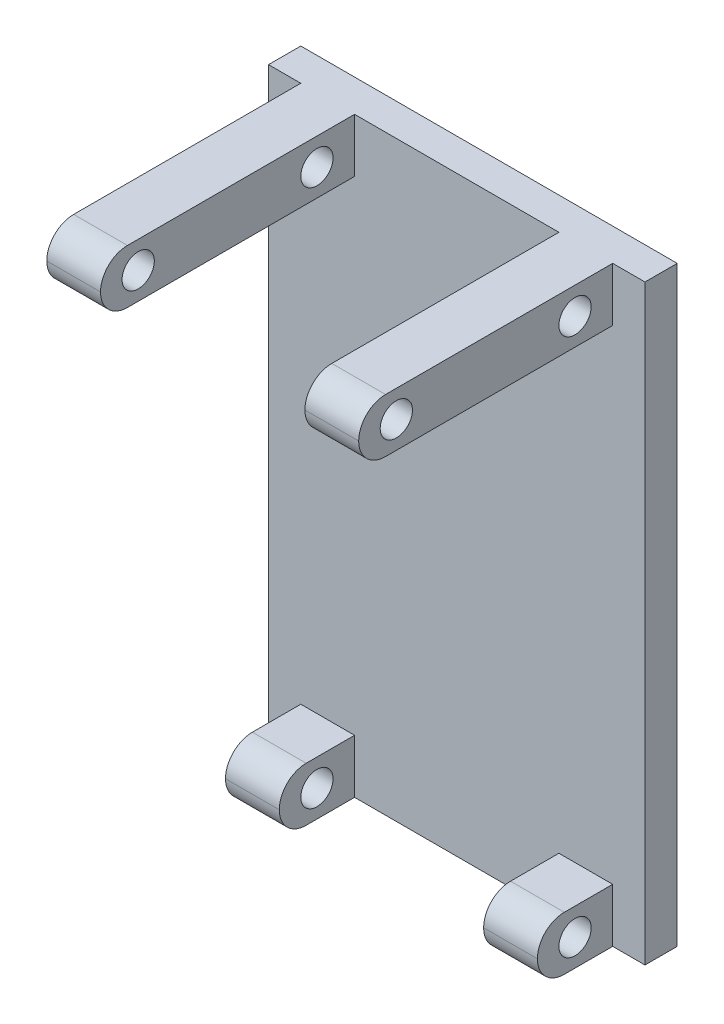
SolidWorks part; units mm, degrees
ref_plane "Front Plane" through (0, 0, 0) normal (0, 0, 1) x (1, 0, 0)
ref_plane "Top Plane" through (0, 0, 0) normal (0, 1, 0) x (1, 0, 0)
ref_plane "Right Plane" through (0, 0, 0) normal (1, 0, 0) x (0, 0, -1)
sketch "Sketch1" plane through (0, 0, 0) normal (0, 0, 1) x (1, 0, 0)
  line L1 (-17.5, -27.5) -> (17.5, -27.5)
  line L2 (-17.5, -27.5) -> (-17.5, 27.5)
  line L3 (-17.5, 27.5) -> (17.5, 27.5)
  line L4 (17.5, -27.5) -> (17.5, 27.5)
  line L5 (-17.5, -27.5) -> (17.5, 27.5) construction
  line L6 (-17.5, 27.5) -> (17.5, -27.5) construction
  point P0 (0, 0)
  dimension "D1" = 35
  dimension "D2" = 55
extrude "Boss-Extrude1" add sketch "Sketch1" along normal blind 3
sketch "Sketch2" plane through (0, 0, 3) normal (0, 0, 1) x (1, 0, 0)
  line L18 (-14.5, 27.5) -> (-9.5, 27.5)
  line L19 (-14.5, 27.5) -> (-14.5, 22.5)
  line L20 (-9.5, 27.5) -> (-9.5, 22.5)
  line L21 (-14.5, 22.5) -> (-9.5, 22.5)
  line L22 (17.5, 27.5) -> (-17.5, 27.5) construction
  line L23 (9.5, 27.5) -> (14.5, 27.5)
  line L24 (9.5, 27.5) -> (9.5, 22.5)
  line L25 (14.5, 27.5) -> (14.5, 22.5)
  line L26 (9.5, 22.5) -> (14.5, 22.5)
  line L27 (-9.5, -27.5) -> (-14.5, -27.5)
  line L28 (-9.5, -27.5) -> (-9.5, -22.5)
  line L29 (-14.5, -27.5) -> (-14.5, -22.5)
  line L30 (-9.5, -22.5) -> (-14.5, -22.5)
  line L31 (-17.5, -27.5) -> (17.5, -27.5) construction
  line L32 (9.5, -27.5) -> (14.5, -27.5)
  line L33 (9.5, -27.5) -> (9.5, -22.5)
  line L34 (14.5, -27.5) -> (14.5, -22.5)
  line L35 (9.5, -22.5) -> (14.5, -22.5)
  line L36 (-17.5, 27.5) -> (-17.5, -27.5) construction
  line L37 (17.5, -27.5) -> (17.5, 27.5) construction
  dimension "D1" = 5
  dimension "D2" = 3
  dimension "D3" = 3
  dimension "D4" = 3
  dimension "D5" = 3
  dimension "D6" = 5
extrude "Boss-Extrude2" add sketch "Sketch2" along normal blind 7
sketch "Sketch3" plane through (-14.5, 0, 0) normal (-1, 0, 0) x (0, 0, 1)
  line L0 (3, 27.5) -> (10, 22.5)
  line L1 (3, -22.5) -> (10, -27.5)
  circle A0 centre (6.5, 25) radius 1.5
  circle A1 centre (6.5, -25) radius 1.5
  dimension "D1" = 3
  dimension "D2" = 3
extrude "Cut-Extrude1" cut sketch "Sketch3" against normal up to surface (29 mm away) contours L0 A0 | L0 A0 | L1 A1 | L1 A1 region at (-14.5, 25.518, 6.87) region at (-14.5, 24.482, 6.13) region at (-14.5, -24.482, 6.87) region at (-14.5, -25.518, 6.13) up to face at (14.5, 25, 6.5)
fillet "Fillet1" radius 2.5 4 edges at (12, -27.5, 10) (12, -22.5, 10) (-12, -27.5, 10) (-12, -22.5, 10)
sketch "Sketch4" plane through (0, 0, 10) normal (0, 0, 1) x (1, 0, 0)
  line L1 (-9.5, 27.5) -> (-14.5, 27.5)
  line L2 (-9.5, 27.5) -> (-9.5, 22.5)
  line L3 (-9.5, 22.5) -> (-14.5, 22.5)
  line L4 (-14.5, 27.5) -> (-14.5, 22.5)
  line L5 (14.5, 27.5) -> (9.5, 27.5)
  line L6 (14.5, 27.5) -> (14.5, 22.5)
  line L7 (14.5, 22.5) -> (9.5, 22.5)
  line L8 (9.5, 27.5) -> (9.5, 22.5)
extrude "Boss-Extrude3" add sketch "Sketch4" along normal blind 16.6176
sketch "Sketch5" plane through (-14.5, 0, 0) normal (-1, 0, 0) x (0, 0, 1)
  line L0 (26.6176, 22.5) -> (3, 22.5) construction
  line L1 (26.6176, 27.5) -> (19.6176, 27.5)
  line L2 (26.6176, 27.5) -> (26.6176, 22.5)
  line L3 (26.6176, 22.5) -> (19.6176, 22.5)
  line L4 (19.6176, 27.5) -> (19.6176, 22.5)
  line L5 (19.6176, 27.5) -> (26.6176, 22.5)
  circle A0 centre (23.1176, 25) radius 1.5
  dimension "D2" = 3
  dimension "D1" = 7
extrude "Cut-Extrude2" cut sketch "Sketch5" against normal up to surface (29 mm away) contours L5 A0 | L5 A0 region at (-14.5, 25.518, 23.4877) region at (-14.5, 24.482, 22.7476) up to face at (14.5, 25, 8)
fillet "Fillet2" radius 2.5 4 edges at (12, 22.5, 26.6176) (12, 27.5, 26.6176) (-12, 22.5, 26.6176) (-12, 27.5, 26.6176)
